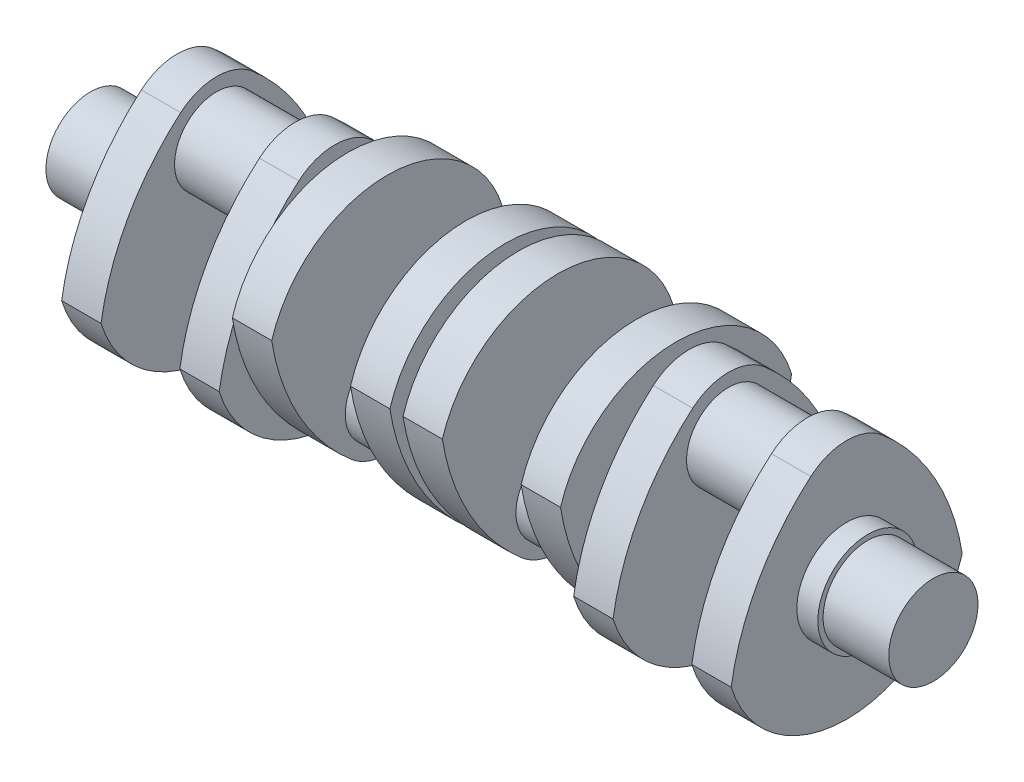
SolidWorks part; units mm, degrees
note: The reader was unsure of these and kept them because the rebuilt part matched: shared geometry of "Sketch1<3>".
ref_plane "Front Plane" through (0, 0, 0) normal (0, 0, 1) x (1, 0, 0)
ref_plane "Top Plane" through (0, 0, 0) normal (0, 1, 0) x (1, 0, 0)
ref_plane "Right Plane" through (0, 0, 0) normal (1, 0, 0) x (0, 0, -1)
sketch "Sketch1" plane through (0, 0, 0) normal (1, 0, 0) x (0, 0, -1)
  circle A0 centre (0, 0) radius 17
  circle A1 centre (0, 0) radius 19
  dimension "D1" = 38
  dimension "D2" = 34
extrude "Boss-Extrude1" add sketch "Sketch1" against normal blind 25 contours A0
extrude "Boss-Extrude2" add sketch "Sketch1<3>" along normal blind 8 contours A1
sketch "Sketch1<3>" plane through (0, 0, 0) normal (1, 0, 0) x (0, 0, -1) same geometry as "Sketch1"
sketch "Sketch2" plane through (8, 0, 0) normal (1, 0, 0) x (0, 0, -1)
  arc A0 (-13.6681, 40.9431) -> (13.6681, 40.9431) centre (0, 25) cw
  arc A1 (-44, -13.4164) -> (44, -13.4164) centre (0, 0) ccw
  arc A2 (-13.6681, 40.9431) -> (-44, -13.4164) centre (44.9095, -27.3845) ccw
  arc A3 (13.6681, 40.9431) -> (44, -13.4164) centre (-44.9095, -27.3845) cw
  dimension "D3" = 46
  dimension "D4" = 21
  dimension "D5" = 90
  dimension "D6" = 90
  dimension "D1" = 25
  dimension "D2" = 88
extrude "Boss-Extrude3" add sketch "Sketch2" along normal blind 15
sketch "Sketch3" plane through (23, 0, 0) normal (1, 0, 0) x (0, 0, -1)
  circle A0 centre (0, 25) radius 16
  dimension "D1" = 32
extrude "Boss-Extrude4" add sketch "Sketch3" along normal blind 15
mirror "Mirror1" about plane through (38, 25, 0) normal (1, 0, 0) of "Boss-Extrude4", "Boss-Extrude3"
sketch "Sketch4" plane through (68, 0, 0) normal (1, 0, 0) x (0, 0, -1)
  circle A0 centre (0, 0) radius 17
  dimension "D1" = 34
extrude "Boss-Extrude5" add sketch "Sketch4" along normal blind 5
sketch "Sketch5" plane through (73, 0, 0) normal (1, 0, 0) x (0, 0, -1)
  arc A8 (-13.6681, -40.9431) -> (13.6681, -40.9431) centre (0, -25) ccw
  arc A9 (-44, 13.4164) -> (-13.6681, -40.9431) centre (44.9095, 27.3845) ccw
  arc A10 (44, 13.4164) -> (-44, 13.4164) centre (0, 0) ccw
  arc A11 (13.6681, -40.9431) -> (44, 13.4164) centre (-44.9095, 27.3845) ccw
extrude "Boss-Extrude6" add sketch "Sketch5" along normal blind 15
sketch "Sketch6" plane through (88, 0, 0) normal (1, 0, 0) x (0, 0, -1)
  circle A0 centre (0, -25) radius 16
  dimension "D1" = 32
  dimension "D2" = 25
extrude "Boss-Extrude7" add sketch "Sketch6" along normal blind 30
sketch "Sketch7" plane through (118, 0, 0) normal (1, 0, 0) x (0, 0, -1)
  arc A4 (-13.6681, -40.9431) -> (13.6681, -40.9431) centre (0, -25) ccw
  arc A5 (13.6681, -40.9431) -> (44, 13.4164) centre (-44.9095, 27.3845) ccw
  arc A6 (44, 13.4164) -> (-44, 13.4164) centre (0, 0) ccw
  arc A7 (-44, 13.4164) -> (-13.6681, -40.9431) centre (44.9095, 27.3845) ccw
  arc A8 (-13.6681, -40.9431) -> (13.6681, -40.9431) centre (0, -25) ccw
  arc A9 (13.6681, -40.9431) -> (44, 13.4164) centre (-44.9095, 27.3845) ccw
  arc A10 (44, 13.4164) -> (-44, 13.4164) centre (0, 0) ccw
  arc A11 (-44, 13.4164) -> (-13.6681, -40.9431) centre (44.9095, 27.3845) ccw
  dimension "D1" = 0
extrude "Boss-Extrude8" add sketch "Sketch7" along normal blind 15
sketch "Sketch8" plane through (133, 0, 0) normal (1, 0, 0) x (0, 0, -1)
  circle A0 centre (0, 0) radius 17
  dimension "D1" = 34
extrude "Boss-Extrude9" add sketch "Sketch8" along normal blind 2.5
mirror "Mirror2" about plane through (135.5, 0, 0) normal (1, 0, 0) of bodies 110
